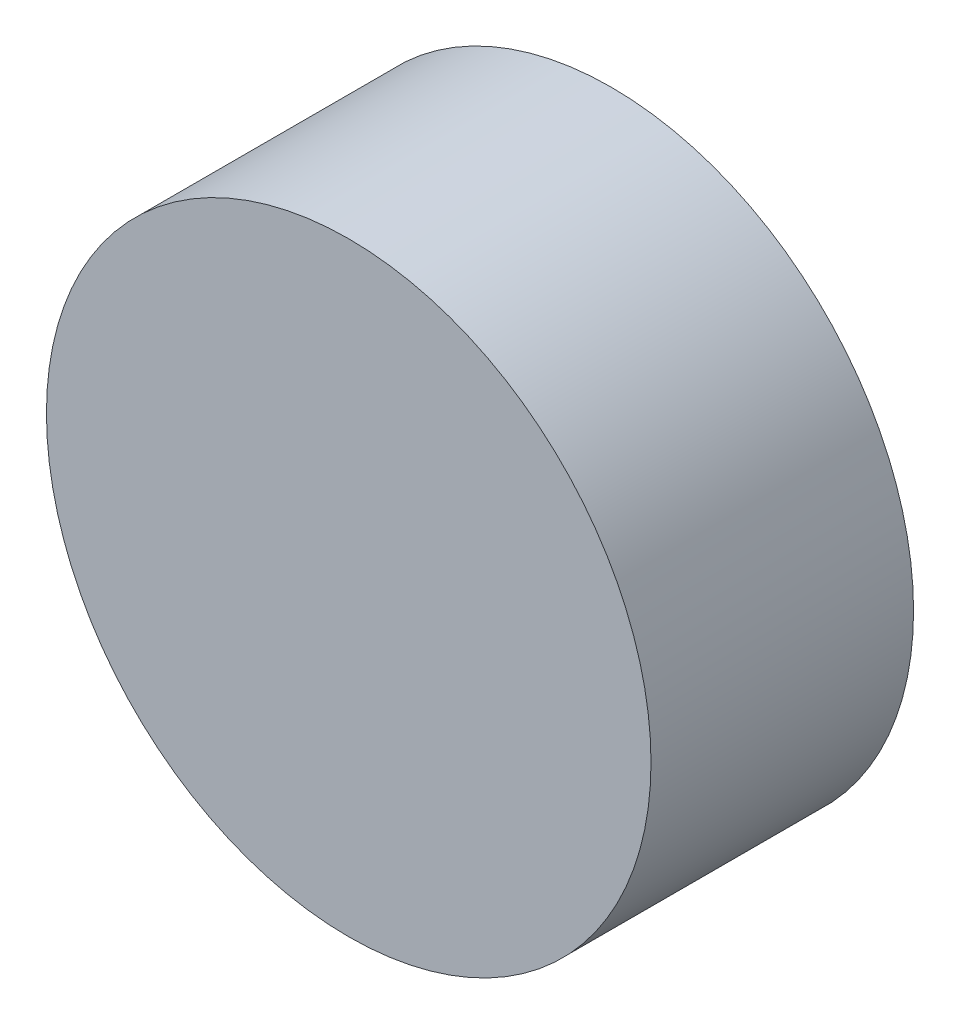
SolidWorks part; units mm, degrees
material "Filter_Bulk_6061Properties"
ref_plane "Front Plane" through (0, 0, 0) normal (0, 0, 1) x (1, 0, 0)
ref_plane "Top Plane" through (0, 0, 0) normal (0, 1, 0) x (1, 0, 0)
ref_plane "Right Plane" through (0, 0, 0) normal (1, 0, 0) x (0, 0, -1)
sketch "Sketch1" plane through (0, 0, 0) normal (0, 0, 1) x (1, 0, 0)
  circle A0 centre (0, 0) radius 13.125
  dimension "D1" = 26.25
extrude "Boss-Extrude1" add sketch "Sketch1" along normal blind 11.4
